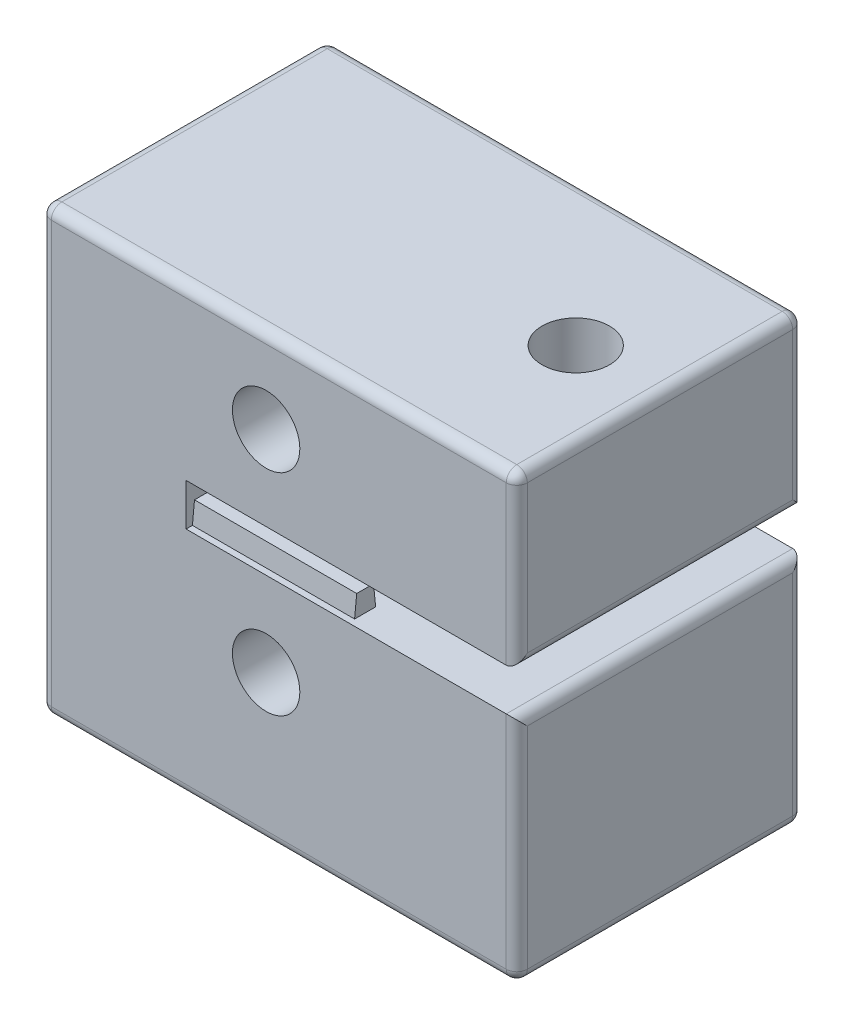
SolidWorks part; units mm, degrees
material "ABS"
ref_plane "Front Plane" through (0, 0, 0) normal (0, 0, 1) x (1, 0, 0)
ref_plane "Top Plane" through (0, 0, 0) normal (0, 1, 0) x (1, 0, 0)
ref_plane "Right Plane" through (0, 0, 0) normal (1, 0, 0) x (0, 0, -1)
sketch "Sketch1" plane through (0, 0, 0) normal (0, 0, 1) x (1, 0, 0)
  line L0 (0, 0) -> (23, 0)
  line L1 (23, 0) -> (23, 11.85)
  line L2 (23, 11.85) -> (40, 11.85)
  line L3 (40, 11.85) -> (40, 22.85)
  line L4 (40, 22.85) -> (24.3, 22.85)
  line L5 (24.3, 22.85) -> (24.3, 24.85)
  line L6 (24.3, 24.85) -> (40, 24.85)
  line L7 (40, 24.85) -> (40, 32.85)
  line L8 (40, 32.85) -> (15.9397, 32.85)
  line L9 (0, 0) -> (0, 13.2554)
  arc A0 (15.9397, 32.85) -> (1.212, 23.6728) centre (5, 34) ccw
  arc A1 (0, 13.2554) -> (1.212, 23.6728) centre (-4, 19) ccw
  circle A2 centre (28.1, 28.85) radius 1.6
  circle A3 centre (28.1, 18.85) radius 1.6
  circle A4 centre (5, 34) radius 5.7
  point P19 (40, 28.85)
  dimension "D1" = 22
  dimension "D8" = 34
  dimension "D9" = 5
  dimension "D12" = 7
  dimension "D14" = 3.2
  dimension "D15" = 10
  dimension "D16" = 11.9
  dimension "D17" = 11.4
  dimension "D2" = 23
  dimension "D3" = 40
  dimension "D4" = 11.85
  dimension "D5" = 11
  dimension "D6" = 8
  dimension "D7" = 2
  dimension "D10" = 19
  dimension "D11" = 4
  dimension "D13" = 15.7
extrude "Boss-Extrude1" add sketch "Sketch1" along normal mid plane 32
sketch "Sketch2" plane through (0, 0, -16) normal (0, 0, -1) x (-1, 0, 0)
  line L0 (0, 0) -> (-15, 0)
  line L1 (0, 0) -> (-23, 0) construction
  line L2 (-15, 0) -> (-15, 16.5)
  line L3 (-15.9397, 32.85) -> (-40, 32.85)
  line L4 (-40, 32.85) -> (-40, 11.85)
  line L5 (-40, 11.85) -> (-23, 11.85)
  line L6 (-23, 11.85) -> (-23, 0)
  line L7 (-23, 0) -> (-15, 0)
  line L8 (-15, 16.5) -> (-2.5383, 16.5)
  line L10 (-15, 17.5) -> (-2.8374, 17.5)
  line L11 (-15, 17.5) -> (-15, 29.4174)
  arc A0 (-15.9397, 32.85) -> (-15, 29.4174) centre (-5, 34) ccw
  arc A1 (-1.212, 23.6728) -> (-15.9397, 32.85) centre (-5, 34) ccw construction
  arc A2 (-1.212, 23.6728) -> (0, 13.2554) centre (4, 19) ccw construction
  arc A3 (-1.212, 23.6728) -> (0, 13.2554) centre (4, 19) ccw
  circle M1 centre (-28.1, 18.85) radius 1.6
  arc M3 (0, 13.2554) -> (-1.212, 23.6728) centre (4, 19) cw
  line M5 (-15.9397, 32.85) -> (-40, 32.85)
  line M6 (-40, 32.85) -> (-40, 24.85)
  line M7 (-40, 24.85) -> (-24.3, 24.85)
  line M8 (-24.3, 24.85) -> (-24.3, 22.85)
  line M9 (-24.3, 22.85) -> (-40, 22.85)
  line M10 (-40, 22.85) -> (-40, 11.85)
  line M11 (-40, 11.85) -> (-23, 11.85)
  line M12 (-23, 11.85) -> (-23, 0)
  line M13 (-23, 0) -> (0, 0)
  circle M14 centre (-28.1, 28.85) radius 1.6
  dimension "D1" = 15
  dimension "D2" = 1
  dimension "D3" = 16.5
extrude "Cut-Extrude1" cut sketch "Sketch2" against normal blind 18.4 contours A0 L2 L8 L10 L11 M5 M6 M7 M8 M9 M10 M11 M12 M13 M3 M1 M14 region at (25.497, 19.4113, -16)
sketch "Sketch3" plane through (0, 0, -16) normal (0, 0, -1) x (-1, 0, 0)
  line L1 (-12.7, 23.5) -> (-4.7, 23.5)
  line L2 (-12.7, 23.5) -> (-12.7, 19.5)
  line L3 (-12.7, 19.5) -> (-4.7, 19.5)
  line L4 (-4.7, 23.5) -> (-4.7, 19.5)
  line L5 (-8.7, 23.5) -> (-8.7, 19.5) construction
  line L6 (-15, 17.5) -> (-15, 29.4174) construction
  line L8 (-15, 17.5) -> (-2.8374, 17.5) construction
  dimension "D1" = 6.3
  dimension "D2" = 8
  dimension "D3" = 4
  dimension "D4" = 2
extrude "Cut-Extrude2" cut sketch "Sketch3" against normal blind 14.9
sketch "Sketch4" plane through (0, 0, 0) normal (0, -1, 0) x (1, 0, 0)
  line L1 (0, -16) -> (15, -16) construction
  line L2 (15, 2.4) -> (15, -16) construction
  circle A0 centre (8.7, -7.6) radius 2.6
  circle A1 centre (8.7, -7.6) radius 6 construction
  dimension "D1" = 6.3
  dimension "D2" = 8.4
  dimension "D3" = 5.2
extrude "Cut-Extrude3" cut sketch "Sketch4" against normal blind 25
sketch "Sketch5" plane through (0, 0, 0) normal (0, -1, 0) x (1, 0, 0)
  circle A0 centre (8.7, -7.6) radius 6
  dimension "D1" = 12
extrude "Cut-Extrude4" cut sketch "Sketch5" against normal blind 6
sketch "Sketch6" plane through (0, 0, 0) normal (-1, 0, 0) x (0, 0, 1)
  line L0 (16, 13.2554) -> (16, 0) construction
  line L1 (16, 0) -> (-16, 0) construction
  circle A0 centre (4.2, 17) radius 4.025
  dimension "D1" = 8.05
  dimension "D2" = 11.8
  dimension "D3" = 17
extrude "Cut-Extrude5" cut sketch "Sketch6" against normal blind 17.4
sketch "Sketch7" plane through (0, 0, -16) normal (0, 0, -1) x (-1, 0, 0)
  circle A0 centre (-5, 34) radius 7.95
  dimension "D1" = 15.9
extrude "Cut-Extrude6" cut sketch "Sketch7" against normal blind 11
sketch "Sketch8" plane through (0, 0, 16) normal (0, 0, 1) x (1, 0, 0)
  circle A0 centre (5, 34) radius 7.95
  dimension "D1" = 15.9
extrude "Cut-Extrude7" cut sketch "Sketch8" against normal blind 11
sketch "Sketch9" plane through (24.3, 0, 0) normal (1, 0, 0) x (0, 0, -1)
  line L0 (-15.7, 22.85) -> (-14.7, 22.85)
  line L1 (-16, 22.85) -> (-2.4, 22.85) construction
  line L2 (-14.7, 22.85) -> (-14.8, 23.85)
  line L3 (-14.8, 23.85) -> (-15.6, 23.85)
  line L4 (-15.6, 23.85) -> (-15.7, 22.85)
  line L5 (-15.2, 23.85) -> (-15.2, 22.85) construction
  line L6 (-13.6, 23.85) -> (-13.7, 22.85)
  line L7 (-13.7, 22.85) -> (-12.7, 22.85)
  line L8 (-12.7, 22.85) -> (-12.8, 23.85)
  line L9 (-12.8, 23.85) -> (-13.6, 23.85)
  line L10 (-11.6, 23.85) -> (-11.7, 22.85)
  line L11 (-11.7, 22.85) -> (-10.7, 22.85)
  line L12 (-10.7, 22.85) -> (-10.8, 23.85)
  line L13 (-10.8, 23.85) -> (-11.6, 23.85)
  line L14 (-9.6, 23.85) -> (-9.7, 22.85)
  line L15 (-9.7, 22.85) -> (-8.7, 22.85)
  line L16 (-8.7, 22.85) -> (-8.8, 23.85)
  line L17 (-8.8, 23.85) -> (-9.6, 23.85)
  line L18 (-7.6, 23.85) -> (-7.7, 22.85)
  line L19 (-7.7, 22.85) -> (-6.7, 22.85)
  line L20 (-6.7, 22.85) -> (-6.8, 23.85)
  line L21 (-6.8, 23.85) -> (-7.6, 23.85)
  line L22 (-5.6, 23.85) -> (-5.7, 22.85)
  line L23 (-5.7, 22.85) -> (-4.7, 22.85)
  line L24 (-4.7, 22.85) -> (-4.8, 23.85)
  line L25 (-4.8, 23.85) -> (-5.6, 23.85)
  line L26 (-3.6, 23.85) -> (-3.7, 22.85)
  line L27 (-3.7, 22.85) -> (-2.7, 22.85)
  line L28 (-2.7, 22.85) -> (-2.8, 23.85)
  line L29 (-2.8, 23.85) -> (-3.6, 23.85)
  dimension "D1" = 0.8
  dimension "D2" = 1
  dimension "D3" = 0.3
  dimension "D4" = 1
  dimension "D5" = 7
extrude "Boss-Extrude2" add sketch "Sketch9" along normal blind 7.7
sketch "Sketch10" plane through (0, 32.85, 0) normal (0, 1, 0) x (1, 0, 0)
  line L0 (40, -16) -> (40, -2.4) construction
  circle A0 centre (36, -9.2) radius 1.6
  point P4 (40, -9.2)
  dimension "D1" = 3.2
  dimension "D2" = 4
extrude "Cut-Extrude8" cut sketch "Sketch10" against normal up to surface (21 mm away) up to face at (31.5, 11.85, 9.2)
sketch "Sketch11" plane through (0, 0, 2.4) normal (0, 0, -1) x (-1, 0, 0)
  line L0 (-23, 11.85) -> (-17.4, 11.85)
  line L1 (-17.4, 11.85) -> (-17.4, 32.85)
  line L2 (-15.9397, 32.85) -> (-40, 32.85) construction
  line L3 (-17.4, 32.85) -> (-17.4, 56.2692)
  line L4 (-17.4, 56.2692) -> (20.0688, 56.2692)
  line L5 (20.0688, 56.2692) -> (20.0688, -12.2316)
  line L6 (20.0688, -12.2316) -> (-23, -11.328)
  line L7 (-23, -11.328) -> (-29.0298, 8.1134)
  line L8 (-29.0298, 8.1134) -> (-23, 11.85)
extrude "Cut-Extrude9" cut sketch "Sketch11" against normal blind 20 and the other way blind 20
fillet "Fillet2" radius 0.5 16 edges at (40, 22.85, 9.2) (40, 24.85, 9.2) (40, 17.35, 2.4) (40, 28.85, 2.4) (28.7, 32.85, 2.4) (17.4, 22.35, 2.4) (28.7, 11.85, 2.4) (40, 11.85, 9.2) (17.4, 11.85, 9.2) (17.4, 32.85, 9.2) (40, 32.85, 9.2) (40, 28.85, 16) (40, 17.35, 16) (28.7, 11.85, 16) (17.4, 22.35, 16) (28.7, 32.85, 16)
equation "\"D1@Sketch4\"=\"D1@Sketch3\""
